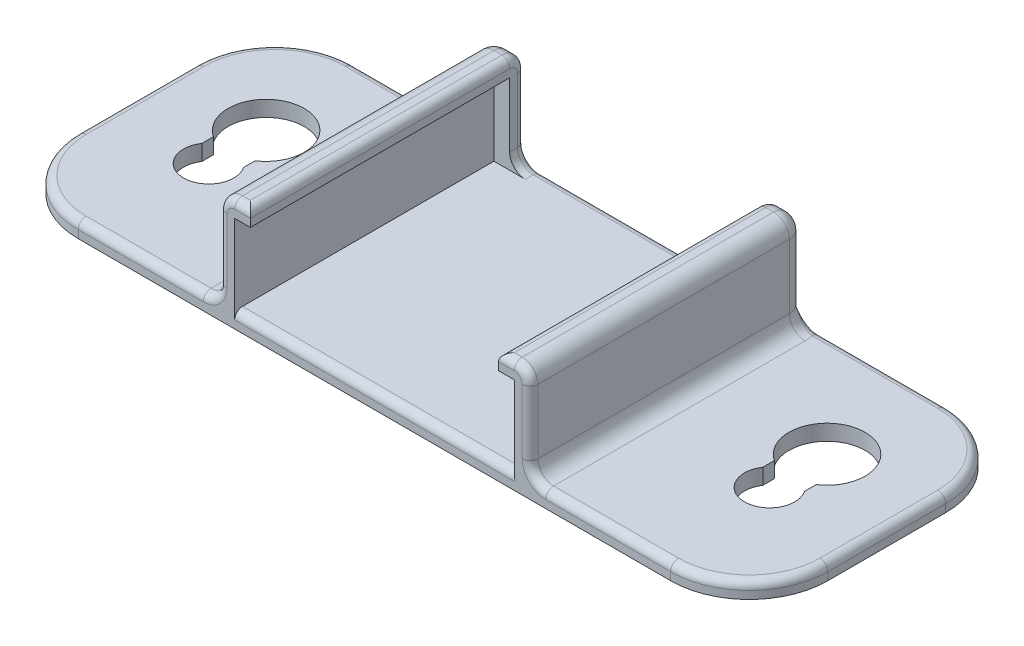
SolidWorks part; units mm, degrees
ref_plane "Front Plane" through (0, 0, 0) normal (0, 0, 1) x (1, 0, 0)
ref_plane "Top Plane" through (0, 0, 0) normal (0, 1, 0) x (1, 0, 0)
ref_plane "Right Plane" through (0, 0, 0) normal (1, 0, 0) x (0, 0, -1)
sketch "Sketch1" plane through (0, 0, 0) normal (0, 1, 0) x (1, 0, 0)
  line L0 (32.5355, 20.405) -> (32.5355, -14.595)
  line L1 (32.5355, 20.405) -> (8.5355, 20.405)
  line L2 (20.5355, 0) -> (20.5355, 7.3093)
  line L3 (8.5355, 20.405) -> (8.5355, -14.595)
  line L4 (79.9355, 20.405) -> (79.9355, -14.595)
  line L5 (8.5355, -14.595) -> (32.5355, -14.595)
  line L6 (79.9355, 20.405) -> (103.9355, 20.405)
  line L7 (103.9355, 20.405) -> (103.9355, -14.595)
  line L8 (79.9355, -14.595) -> (103.9355, -14.595)
  line L9 (23.1932, 1.7823) -> (23.1932, 3.2627)
  line L10 (17.8778, 1.7823) -> (17.8778, 3.2627)
  line L11 (94.5932, 1.7823) -> (94.5932, 3.2627)
  line L12 (89.2778, 1.7823) -> (89.2778, 3.2627)
  line L13 (91.9355, 0.9079) -> (91.9355, 8.2172)
  line L14 (37.5355, 20.405) -> (37.5355, -14.595) construction
  line L15 (91.9355, 20.405) -> (91.9355, -14.595) construction
  line L16 (20.5355, 20.405) -> (20.5355, -14.595) construction
  line L21 (74.9355, 25.9512) -> (74.9355, -14.595) construction
  line L22 (32.5355, 20.405) -> (79.9355, 20.405)
  line L23 (32.5355, -14.595) -> (79.9355, -14.595)
  arc A0 (17.8778, 1.7823) -> (23.1932, 1.7823) centre (20.5355, 0) ccw
  arc A1 (23.1932, 3.2627) -> (17.8778, 3.2627) centre (20.5355, 7.3093) ccw
  arc A2 (94.5932, 3.2627) -> (89.2778, 3.2627) centre (91.9355, 7.3093) ccw
  arc A3 (89.2778, 1.7823) -> (94.5932, 1.7823) centre (91.9355, 0) ccw
  dimension "D1" = 5
  dimension "D2" = 24
  dimension "D3" = 24
  dimension "D4" = 35
  dimension "D6" = 37.4
  dimension "D8" = 5
extrude "Boss-Extrude3" add sketch "Sketch1" along normal blind 2
sketch "Sketch6" plane through (0, 2, 0) normal (0, 1, 0) x (1, 0, 0)
  line L4 (56.2355, 20.405) -> (56.2355, -14.595) construction
  line L5 (103.9355, 20.405) -> (8.5355, 20.405) construction
  line L6 (8.5355, -14.595) -> (103.9355, -14.595) construction
  line L7 (76.0355, 20.405) -> (76.0355, -14.595)
  line L8 (38.4355, 20.405) -> (36.4355, 20.405)
  line L9 (38.4355, 20.405) -> (38.4355, -14.595)
  line L10 (38.4355, -14.595) -> (36.4355, -14.595)
  line L11 (36.4355, 20.405) -> (36.4355, -14.595)
  line L12 (74.0355, -14.595) -> (76.0355, -14.595)
  line L13 (74.0355, 20.405) -> (74.0355, -14.595)
  line L14 (74.0355, 20.405) -> (76.0355, 20.405)
  dimension "D1" = 2
  dimension "D2" = 35.6
extrude "Boss-Extrude8" add sketch "Sketch6" along normal blind 12.2
fillet "Fillet15" radius 10 4 edges at (103.9355, 1, 14.595) (8.5355, 1, 14.595) (8.5355, 1, -20.405) (103.9355, 1, -20.405)
sketch "Sketch7" plane through (74.0355, 0, 0) normal (-1, 0, 0) x (0, 0, 1)
  line L0 (-20.405, 14.2) -> (-20.405, 2) construction
  line L1 (14.595, 14.2) -> (-20.405, 14.2)
  line L2 (14.595, 14.2) -> (14.595, 12.2)
  line L3 (14.595, 12.2) -> (-20.405, 12.2)
  line L4 (-20.405, 14.2) -> (-20.405, 12.2)
  line L5 (-20.405, 2) -> (14.595, 2) construction
  line L6 (-20.405, 12.2) -> (-18.405, 12.2)
  line L7 (-20.405, 12.2) -> (-20.405, 2)
  line L8 (-20.405, 2) -> (-18.405, 2)
  line L9 (-18.405, 12.2) -> (-18.405, 2)
  dimension "D1" = 2
  dimension "D2" = 2
extrude "Boss-Extrude9" add sketch "Sketch7" along normal blind 2 contours L7 L8 L9 L6 | L3 L2 L1 L4
sketch "Sketch8" plane through (38.4355, 0, 0) normal (1, 0, 0) x (0, 0, -1)
  line L0 (20.405, 14.2) -> (20.405, 2) construction
  line L1 (-14.595, 14.2) -> (20.405, 14.2)
  line L2 (-14.595, 14.2) -> (-14.595, 12.2)
  line L3 (-14.595, 12.2) -> (20.405, 12.2)
  line L4 (20.405, 14.2) -> (20.405, 12.2)
  line L6 (20.405, 12.2) -> (18.405, 12.2)
  line L7 (20.405, 12.2) -> (20.405, 1.6037)
  line L8 (20.405, 1.6037) -> (18.405, 1.6037)
  line L9 (18.405, 12.2) -> (18.405, 1.6037)
  line M5 (-14.595, 2) -> (20.405, 2)
  line M6 (20.405, 2) -> (20.405, 14.2)
  line M7 (20.405, 14.2) -> (-14.595, 14.2)
  line M8 (-14.595, 14.2) -> (-14.595, 2)
  dimension "D1" = 2
  dimension "D2" = 2
extrude "Boss-Extrude10" add sketch "Sketch8" along normal blind 2 contours L3 M8 M6 M7 | L3 L9 M5 M6
fillet "Fillet16" radius 2 2 edges at (76.0355, 8.1, -20.405)
fillet "Fillet17" radius 2 16 edges at (72.0355, 2, -19.405) (40.4355, 2, -19.405) (73.0355, 14.2, -20.405) (75.4497, 14.2, -19.8192) (36.4355, 14.2, -1.905) (37.0213, 14.2, -19.8192) (75.4497, 2, -19.8192) (37.0213, 2, -19.8192) (39.4355, 14.2, -20.405) (76.0355, 2, -1.905) (76.0355, 14.2, -1.905)
fillet "Fillet18" radius 1 31 edges at (72.0355, 14.2, -1.905) (72.0355, 8.1, -20.405) (72.0355, 13.6142, -19.8192) (40.4355, 8.1, -20.405) (39.4355, 14.2, 14.595) (40.4355, 14.2, -1.905) (40.4355, 13.6142, -19.8192) (76.0355, 8.1, 14.595) (37.0213, 13.6142, 14.595) (75.4497, 13.6142, 14.595) (76.4996, 2.1787, -20.405) (35.9714, 2.1787, -20.405) (41.0213, 2.5858, -20.405) (71.4497, 2.5858, -20.405) (76.6213, 2.5858, 14.595) (35.8497, 2.5858, 14.595) (73.0355, 14.2, 14.595) (103.9355, 2, -2.905) (101.0066, 2, -17.4761) (101.0066, 2, 11.6661) (8.5355, 2, -2.905) (11.4644, 2, -17.4761) (11.4644, 2, 11.6661)
